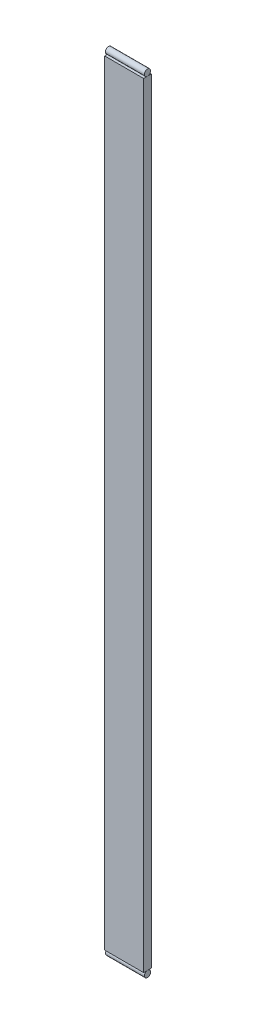
SolidWorks part; units mm, degrees
ref_plane "Front Plane" through (0, 0, 0) normal (0, 0, 1) x (1, 0, 0)
ref_plane "Top Plane" through (0, 0, 0) normal (0, 1, 0) x (1, 0, 0)
ref_plane "Right Plane" through (0, 0, 0) normal (1, 0, 0) x (0, 0, -1)
sketch "Sketch1" plane through (0, 0, 0) normal (0, 1, 0) x (1, 0, 0)
  line L1 (-25, -5) -> (25, -5)
  line L2 (-25, -5) -> (-25, 5)
  line L3 (-25, 5) -> (25, 5)
  line L4 (25, -5) -> (25, 5)
  line L5 (-25, -5) -> (25, 5) construction
  line L6 (-25, 5) -> (25, -5) construction
  point P0 (0, 0)
  dimension "D1" = 50
  dimension "D2" = 10
extrude "Boss-Extrude1" add sketch "Sketch1" along normal blind 992
sketch "Sketch2" plane through (25, 0, 0) normal (1, 0, 0) x (0, 0, -1)
  line L0 (-5, 992) -> (5, 992) construction
  line L1 (0, 996) -> (0, 992) construction
  line L2 (-5, 992) -> (-5, 0) construction
  line L3 (0, -4) -> (0, 0) construction
  line L4 (-5, 0) -> (5, 0) construction
  circle A0 centre (0, 996) radius 4
  circle A1 centre (0, -4) radius 4
  dimension "D1" = 8
  dimension "D3" = 8
  dimension "D2" = 5
extrude "Boss-Extrude2" add sketch "Sketch2" against normal up to surface (50 mm away) separate body up to face at (-25, 496, 0)
ref_point "Point1"
ref_point "Point2"
ref_axis "Axis2" through (0, 996, 0) along (0, -1, 0)
ref_point "Point3"
ref_point "Point4"
ref_point "Point5"
ref_point "Point6"
